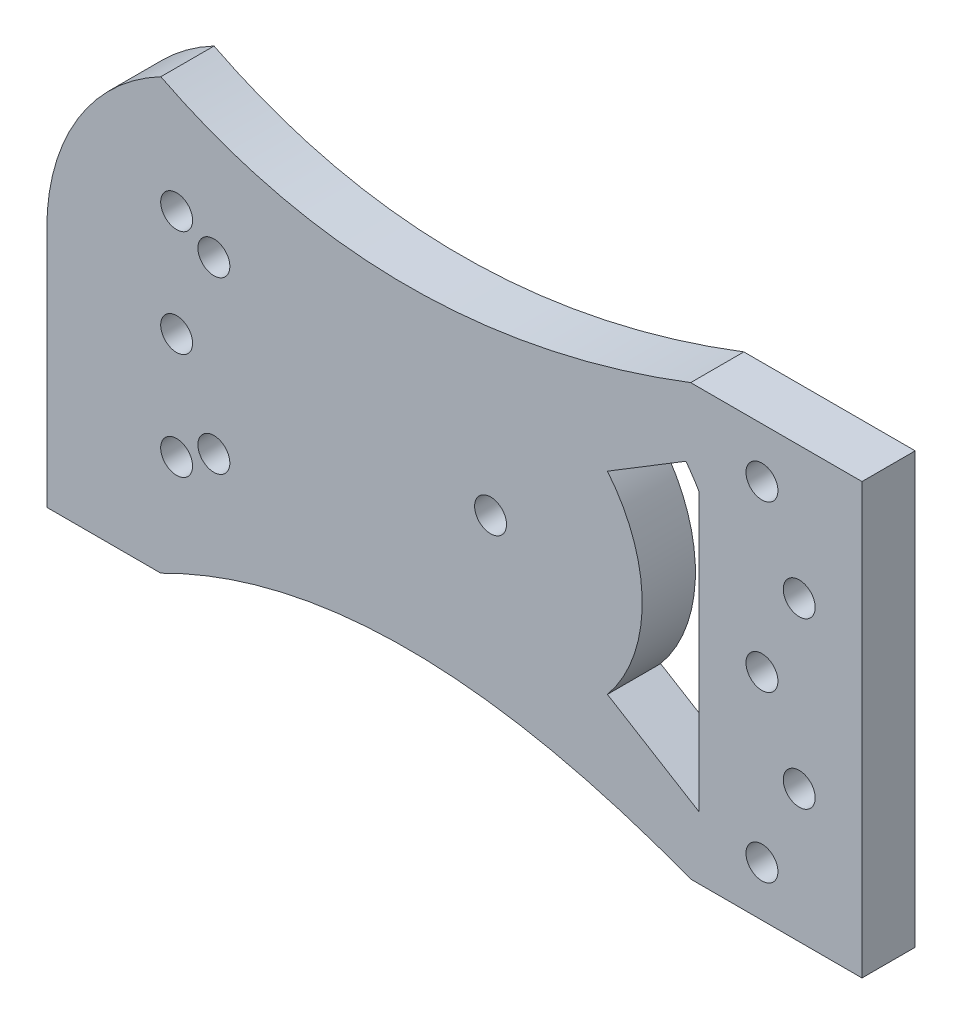
SolidWorks part; units mm, degrees
ref_plane "Alzado" through (0, 0, 0) normal (0, 0, 1) x (1, 0, 0)
ref_plane "Planta" through (0, 0, 0) normal (0, 1, 0) x (1, 0, 0)
ref_plane "Vista lateral" through (0, 0, 0) normal (1, 0, 0) x (0, 0, -1)
sketch "Croquis1" plane through (0, 0, 0) normal (0, 0, 1) x (1, 0, 0)
  line L0 (69.9838, -20.2) -> (69.9838, -20) construction
  line L1 (72.9, -20.2) -> (31.5, -20.2)
  line L2 (72.9, -20.2) -> (72.9, 20.2)
  line L3 (72.9, 20.2) -> (31.5, 20.2)
  line L4 (31.5, -20.2) -> (31.5, 20.2)
  line L5 (72.9, -20) -> (2.6, -20) construction
  line L6 (69.9838, 20) -> (69.9838, 20.2) construction
  line L7 (72.9, 20) -> (2.6, 20) construction
  line L8 (72.9, 20) -> (72.9, -20) construction
  line L9 (36.5, -20) -> (36.5, 20) construction
  circle A0 centre (63.5, 0) radius 1.5
  circle A1 centre (38, 0) radius 1.5 construction
  circle A2 centre (63.5, -15.5) radius 1.5
  circle A3 centre (38, 0) radius 1.5
  circle A4 centre (63.5, 15.5) radius 1.5
  circle A5 centre (67, -7.75) radius 1.5
  circle A6 centre (67, 7.75) radius 1.5
  point P18 (36.5, 0)
  dimension "D3" = 3
  dimension "D1" = 0.2
  dimension "D2" = 5
extrude "Saliente-Extruir1" add sketch "Croquis1" along normal blind 5
sketch "Croquis2" plane through (72.9, 0, 0) normal (1, 0, 0) x (0, 0, -1)
  line L0 (-5, -20.2) -> (-5, -25.2)
  line L1 (-5, -25.2) -> (45.2, -25.2)
  line L2 (45.2, -25.2) -> (45.2, 25.2)
  line L3 (45.2, 25.2) -> (-5, 25.2)
  line L4 (-5, 25.2) -> (-5, 20.2)
  line L5 (-5, 20.2) -> (0, 20.2)
  line L6 (0, 20.2) -> (40.2, 20.2)
  line L7 (40.2, 20.2) -> (40.2, -20.2)
  line L8 (40.2, -20.2) -> (0, -20.2)
  line L9 (20, 20) -> (20, 20.2) construction
  line L10 (0, 20) -> (40, 20) construction
  line L11 (40.2, 0) -> (45.2, 0) construction
  line L12 (-5, 0) -> (0, 0) construction
  line L13 (-5, -20.2) -> (-5, 20.2) construction
  line L14 (40.2, 0) -> (40, 0) construction
  line L15 (40, 20) -> (40, -20) construction
  line L16 (0, -20.2) -> (-5, -20.2)
extrude "Saliente-Extruir2" [suppressed] add sketch "Croquis2" against normal up to surface (41.4 mm away)
sketch "Croquis3" plane through (0, 0, 5) normal (0, 0, 1) x (1, 0, 0)
  line L0 (31.5, -20.2) -> (72.9, -20.2) construction
  line L1 (31.5, 20.2) -> (-3.7, 20.2)
  line L2 (31.5, 20.2) -> (31.5, -20.2)
  line L3 (31.5, -20.2) -> (-3.7, -20.2)
  line L4 (-3.7, 20.2) -> (-3.7, -20.2)
  line L5 (-3.4, 10.4) -> (-3.4, -10.4) construction
  circle A0 centre (8.5, 0) radius 1.5
  circle A1 centre (8.5, -10) radius 1.5
  circle A2 centre (8.5, 10) radius 1.5
  circle A3 centre (38, 0) radius 1.5 construction
  circle A4 centre (12, 8) radius 1.5
  circle A5 centre (12, -8) radius 1.5
  dimension "D1" = 0.3
extrude "Saliente-Extruir3" add sketch "Croquis3" against normal up to surface (5 mm away) up to face at (52.2, 0, 0)
sketch "Croquis5" plane through (0, 0, 5) normal (0, 0, 1) x (1, 0, 0)
  line L0 (72.9, 20.2) -> (-3.7, 20.2) construction
  line L1 (56.8, -39) -> (56.8, 39) construction
  line L2 (7.015, 20.2) -> (56.8, 20.2)
  spline S0 degree 2 poles (56.8, 20.2) (28.4696, 9.3229) (7.015, 20.2) knots 0 0 0 0.7936 0.7936 0.7936
extrude "Cortar-Extruir1" cut sketch "Croquis5" against normal up to next
mirror "Simetría1" about plane through (0, 0, 0) normal (0, 1, 0) of "Cortar-Extruir1"
fillet "Redondeo1" radius 20 1 edges at (-3.7, 20.2, 2.5)
sketch "Croquis6" plane through (0, 0, 5) normal (0, 0, 1) x (1, 0, 0)
  line L0 (57.6063, 14.3422) -> (57.6063, -14.3422)
  line L1 (57.6063, -14.3422) -> (48.9778, -9.0822)
  line L2 (57.6063, 14.3422) -> (48.9778, 9.0822)
  line L3 (38, 0) -> (57.6063, 0) construction
  line L4 (21.2631, 7.9786) -> (21.2631, -7.9786) construction
  line L5 (21.2631, -7.9786) -> (21.2631, 0) construction
  line L6 (21.2631, 0) -> (38, 0) construction
  circle A0 centre (38, 0) radius 14.2478
  circle A1 centre (38, 0) radius 22.8349
  circle A2 centre (21.2631, 7.9786) radius 4.2936
  circle A3 centre (21.2631, -7.9786) radius 4.2936
  point P6 (57.6063, 0)
extrude "Cortar-Extruir2" cut sketch "Croquis6" against normal up to next contours A0 L3 L0 L2 | L3 A0 L1 L0
ref_plane "Plano1" through (36.5, 0, 0) normal (1, 0, 0) x (0, 0, -1)
